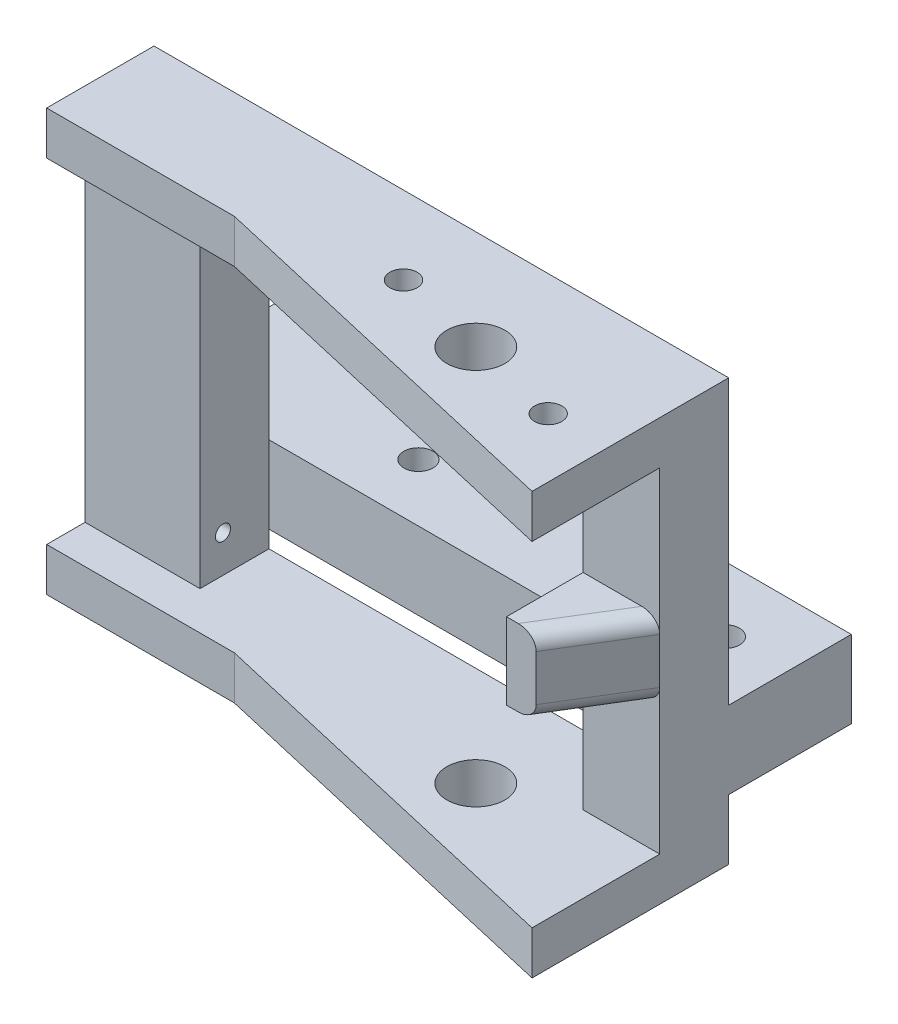
SolidWorks part; units mm, degrees
ref_plane "Front Plane" through (0, 0, 0) normal (0, 0, 1) x (1, 0, 0)
ref_plane "Top Plane" through (0, 0, 0) normal (0, 1, 0) x (1, 0, 0)
ref_plane "Right Plane" through (0, 0, 0) normal (1, 0, 0) x (0, 0, -1)
sketch "Sketch1" plane through (0, 0, 0) normal (0, 0, 1) x (1, 0, 0)
  line L1 (57.15, -34.925) -> (-57.15, -34.925)
  line L2 (57.15, -34.925) -> (57.15, 34.925)
  line L3 (57.15, 34.925) -> (-57.15, 34.925)
  line L4 (-57.15, -34.925) -> (-57.15, 34.925)
  line L5 (57.15, -34.925) -> (-57.15, 34.925) construction
  line L6 (57.15, 34.925) -> (-57.15, -34.925) construction
  point P0 (0, 0)
  dimension "D1" = 69.85
  dimension "D2" = 114.3
extrude "Boss-Extrude1" add sketch "Sketch1" along normal blind 57.15
sketch "Sketch2" plane through (0, 0, 57.15) normal (0, 0, 1) x (1, 0, 0)
  line L0 (-57.15, 34.925) -> (-57.15, -34.925) construction
  line L1 (57.15, -27.725) -> (-57.15, -27.725)
  line L2 (57.15, -27.725) -> (57.15, 27.725)
  line L3 (57.15, 27.725) -> (-57.15, 27.725)
  line L4 (-57.15, -27.725) -> (-57.15, 27.725)
  line L5 (57.15, -27.725) -> (-57.15, 27.725) construction
  line L6 (57.15, 27.725) -> (-57.15, -27.725) construction
  line L7 (57.15, 34.925) -> (-57.15, 34.925) construction
  point P0 (0, 0)
  dimension "D1" = 7.2
extrude "Cut-Extrude2" cut sketch "Sketch2" against normal blind 25.4
sketch "Sketch3" plane through (0, 0, 0) normal (0, 0, -1) x (-1, 0, 0)
  line L0 (-57.15, -34.925) -> (-57.15, 34.925) construction
  line L1 (57.15, 34.925) -> (-57.15, 34.925)
  line L2 (57.15, 34.925) -> (57.15, -12.065)
  line L3 (57.15, -12.065) -> (-57.15, -12.065)
  line L4 (-57.15, 34.925) -> (-57.15, -12.065)
  dimension "D1" = 46.99
extrude "Cut-Extrude3" cut sketch "Sketch3" against normal blind 20.32
sketch "Sketch5" plane through (0, -34.925, 0) normal (0, -1, 0) x (1, 0, 0)
  line L0 (-3.81, 10.79) -> (46.99, 10.79) construction
  line L1 (57.15, 20.32) -> (-57.15, 20.32) construction
  line L2 (57.15, 57.15) -> (57.15, 0) construction
  circle A0 centre (-3.81, 10.79) radius 2.415
  circle A1 centre (46.99, 10.79) radius 2.415
  dimension "D3" = 4.83
  dimension "D4" = 10.16
  dimension "D1" = 9.53
  dimension "D2" = 50.8
sketch "Sketch7" plane through (0, -34.925, 0) normal (0, -1, 0) x (1, 0, 0)
  line L0 (57.15, 57.15) -> (57.15, 0) construction
  line L2 (-57.15, 31.75) -> (57.15, 31.75) construction
  circle A0 centre (31.75, 36.83) radius 4.8
  dimension "D1" = 9.6
  dimension "D2" = 25.4
  dimension "D3" = 5.08
extrude "Cut-Extrude6" cut sketch "Sketch7" against normal up to surface (69.85 mm away) up to face at (0, 34.925, 38.735)
sketch "Sketch8" plane through (0, 34.925, 0) normal (0, 1, 0) x (1, 0, 0)
  line L0 (16.1601, -33.2308) -> (47.3399, -40.4292) construction
  line L1 (57.15, -31.75) -> (-57.15, -31.75) construction
  circle A0 centre (31.75, -36.83) radius 16 construction
  circle A1 centre (16.1601, -33.2308) radius 2.25
  circle A2 centre (47.3399, -40.4292) radius 2.25
  dimension "D1" = 32
  dimension "D2" = 4.5
  dimension "D3" = 13
sketch "Sketch9" plane through (0, 0, 31.75) normal (0, 0, 1) x (1, 0, 0)
  line L0 (57.15, 34.925) -> (-57.15, 34.925) construction
  line L5 (57.15, 27.725) -> (-57.15, 27.725) construction
  line L6 (-19.05, 27.725) -> (44.45, 27.725)
  line L7 (-19.05, 27.725) -> (-19.05, -27.725)
  line L8 (-19.05, -27.725) -> (44.45, -27.725)
  line L9 (44.45, 27.725) -> (44.45, -27.725)
  line L10 (-57.15, -27.725) -> (57.15, -27.725) construction
  line L11 (-57.15, 27.725) -> (-57.15, -27.725) construction
  line L12 (57.15, -27.725) -> (57.15, 27.725) construction
  line L13 (-57.15, -34.925) -> (-38.1, -34.925)
  line L14 (-57.15, -34.925) -> (-57.15, 34.925)
  line L15 (-57.15, 34.925) -> (-38.1, 34.925)
  line L16 (-38.1, -34.925) -> (-38.1, 34.925)
  line L17 (-57.15, -34.925) -> (-38.1, 34.925) construction
  line L18 (-57.15, 34.925) -> (-38.1, -34.925) construction
  line L19 (-57.15, -34.925) -> (57.15, -34.925) construction
  point P5 (-47.625, 0)
  dimension "D1" = 12.7
  dimension "25in" = 38.1
  dimension "D2" = 19.05
extrude "Cut-Extrude7" cut sketch "Sketch9" against normal through all both and the other way through all
extrude "Cut-Extrude8" cut sketch "Sketch8" against normal up to next
sketch "Sketch10" [suppressed] plane through (0, 0, 29.21) normal (0, 0, 1) x (1, 0, 0)
  line L1 (-30.607, -1.778) -> (-30.607, -6.604) construction
  circle A0 centre (-33.2489, -4.191) radius 2.286
  point P5 (-30.607, -4.191)
  dimension "D1" = 4.572
sketch "Sketch11" [suppressed] plane through (0, 0, 20.32) normal (0, 0, -1) x (-1, 0, 0)
  circle A0 centre (33.2489, -4.191) radius 2.286
  dimension "D1" = 4.572
extrude "Cut-Extrude9" [suppressed] cut sketch "Sketch11" against normal blind 3.81
sketch "Sketch12" plane through (-19.05, 0, 0) normal (1, 0, 0) x (0, 0, -1)
  line L0 (-31.75, -27.725) -> (-31.75, 27.725) construction
  line L1 (-27.94, -21.59) -> (-27.94, 21.59) construction
  line L2 (-20.32, 27.725) -> (-20.32, -12.065) construction
  circle A0 centre (-27.94, -21.59) radius 1.25
  circle A1 centre (-27.94, 21.59) radius 1.25
  point P0 (-31.75, 0)
  point P8 (-27.94, 0)
  dimension "D1" = 2.5
  dimension "D2" = 7.62
  dimension "D3" = 43.18
extrude "Cut-Extrude10" cut sketch "Sketch12" against normal up to surface (19.05 mm away) up to face at (-38.1, -2.413, 33.274)
sketch "Sketch13" plane through (0, 34.925, 0) normal (0, 1, 0) x (1, 0, 0)
  line L0 (-38.1, -38.1077) -> (-6.9983, -38.1077)
  line L1 (-6.9983, -38.1077) -> (75.4829, -57.15)
  line L2 (57.15, -57.15) -> (-38.1, -57.15) construction
  line L3 (47.3399, -40.4292) -> (16.1601, -33.2308) construction
  line L4 (-38.1, -38.1077) -> (-38.1, -57.15)
  line L5 (-38.1, -57.15) -> (75.4829, -57.15)
  line L6 (-38.1, -20.32) -> (-38.1, -57.15) construction
extrude "Cut-Extrude12" cut sketch "Sketch13" against normal through all
sketch "Sketch14" plane through (44.45, 0, 0) normal (-1, 0, 0) x (0, 0, 1)
  line L0 (0, -27.725) -> (31.75, -27.725) construction
  line L1 (20.32, -12.065) -> (0, -12.065)
  line L2 (20.32, -12.065) -> (20.32, -27.725)
  line L3 (20.32, -27.725) -> (0, -27.725)
  line L4 (0, -12.065) -> (0, -27.725)
extrude "Boss-Extrude2" add sketch "Sketch14" along normal up to next
sketch "Sketch16" plane through (0, 0, 31.75) normal (0, 0, 1) x (1, 0, 0)
  line L0 (44.45, -27.725) -> (44.45, 27.725) construction
  line L1 (57.15, -6.35) -> (44.45, -6.35)
  line L2 (57.15, -6.35) -> (57.15, 6.35)
  line L3 (57.15, 6.35) -> (44.45, 6.35)
  line L4 (44.45, -6.35) -> (44.45, 6.35)
  line L5 (57.15, -6.35) -> (44.45, 6.35) construction
  line L6 (57.15, 6.35) -> (44.45, -6.35) construction
  line L7 (57.15, 6.35) -> (57.15, -6.35) construction
  line L9 (57.15, -27.725) -> (57.15, 27.725) construction
  point P0 (50.8, 0)
  point P7 (57.15, 0)
  dimension "D1" = 12.7
extrude "Boss-Extrude3" add sketch "Sketch16" along normal blind 12.7
sketch "Sketch17" plane through (0, 6.35, 0) normal (0, 1, 0) x (1, 0, 0)
  line L0 (49.375, -44.45) -> (57.15, -31.75)
  line L1 (57.15, -44.45) -> (57.15, -31.75) construction
  line L2 (57.15, -31.75) -> (44.45, -31.75) construction
  line L3 (57.15, -31.75) -> (57.15, -44.45)
  line L4 (57.15, -44.45) -> (49.375, -44.45)
  line L5 (57.15, -44.45) -> (44.45, -44.45) construction
extrude "Cut-Extrude14" cut sketch "Sketch17" against normal blind 12.7
fillet "Fillet4" radius 2.54 2 edges at (53.2625, -6.35, 38.1) (53.2625, 6.35, 38.1)
sketch "Sketch18" plane through (-38.1, 0, 0) normal (-1, 0, 0) x (0, 0, 1)
  line L0 (0, -34.925) -> (38.1077, -34.925) construction
  line L1 (20.32, -35.0627) -> (20.32, -24.9001)
  line L2 (20.32, -24.9001) -> (0, -24.9001)
  line L3 (0, -34.925) -> (0, -12.065) construction
  line L4 (0, -24.9001) -> (0, -34.925)
  line L5 (20.32, -34.925) -> (0, -34.925)
  point P0 (20.32, -34.925)
  point P1 (7.9478, 3.6724)
  line M3 (0, -34.925) -> (38.1077, -34.925)
  line M12 (0, -12.065) -> (0, -34.925)
sketch "Sketch19" plane through (-38.1, 0, 0) normal (-1, 0, 0) x (0, 0, 1)
  line L0 (20.32, -34.925) -> (0, -34.925)
sketch "Sketch20" plane through (-38.1, 0, 0) normal (-1, 0, 0) x (0, 0, 1)
  line L0 (0, -34.925) -> (38.1077, -34.925) construction
  line L1 (20.066, -34.925) -> (20.066, -24.765)
  line L2 (20.066, -24.765) -> (0, -24.765)
  line L3 (0, -34.925) -> (0, -12.065) construction
  line L4 (0, -24.765) -> (0, -34.925)
  line L5 (20.066, -34.925) -> (-0.1509, -34.925)
  point P0 (20.32, -34.925)
  dimension "D1" = 10.16
  dimension "D2" = 20.066
extrude "Cut-Extrude20" cut sketch "Sketch5" against normal through all contours A0 | A1
sketch "Sketch21" plane through (-38.1, 0, 0) normal (-1, 0, 0) x (0, 0, 1)
sketch "Sketch22" plane through (-38.1, 0, 0) normal (-1, 0, 0) x (0, 0, 1)
extrude "Cut-Extrude21" cut sketch "Sketch18" against normal through all contours L1 L2 M12 M3 region at (-38.1, -29.9125, 10.16)
